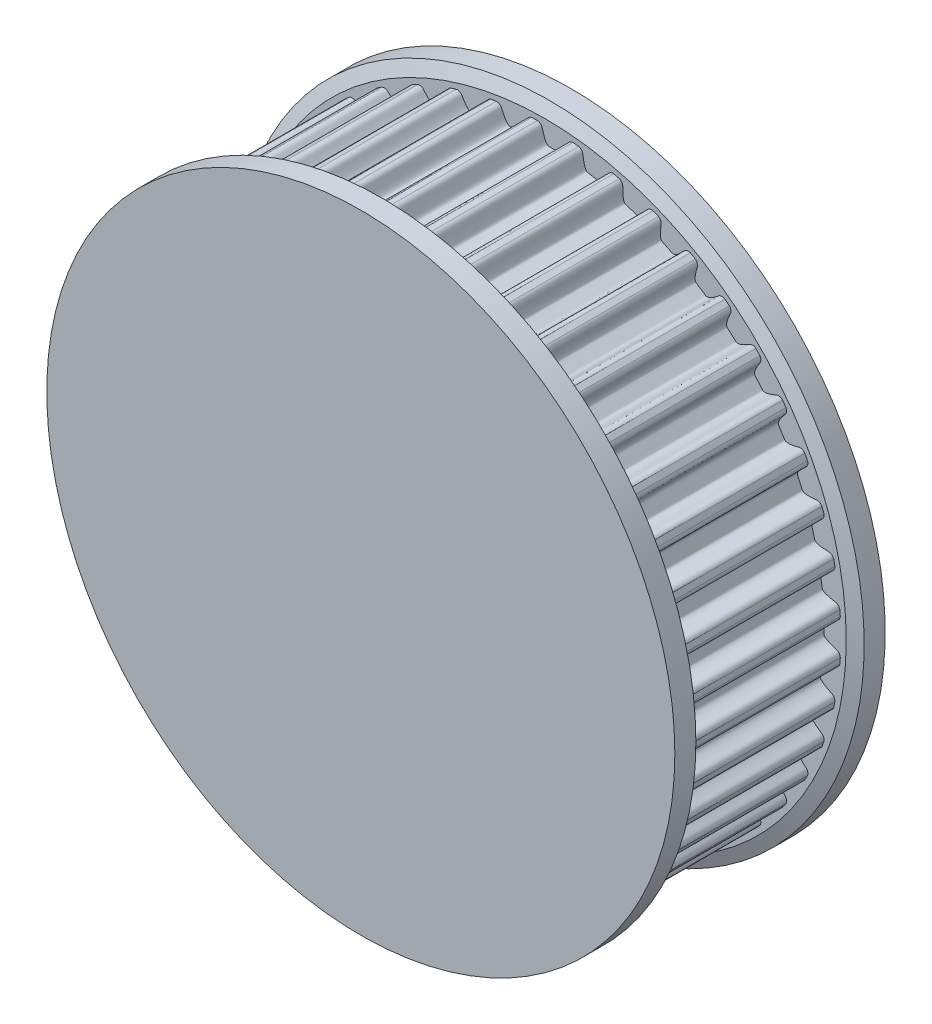
SolidWorks part; units mm, degrees
ref_plane "Front Plane" through (0, 0, 0) normal (0, 0, 1) x (1, 0, 0)
ref_plane "Top Plane" through (0, 0, 0) normal (0, 1, 0) x (1, 0, 0)
ref_plane "Right Plane" through (0, 0, 0) normal (1, 0, 0) x (0, 0, -1)
ref_axis "Axis1" through (0, 0, 55) along (0, 0, -1)
sketch "SketchRevolveGearBelt01" plane through (0, 0, 0) normal (1, 0, 0) x (0, 0, -1)
  line L0 (0, 0) -> (1, 0) construction
  line L1 (5.274, 0) -> (5.274, 12.8239)
  line L2 (5.274, 12.8239) -> (4.512, 12.8239)
  line L3 (4.512, 12.8239) -> (4.512, 14.1724)
  line L4 (4.512, 14.1724) -> (4.7696, 14.7943)
  line L5 (4.7696, 14.7943) -> (4.0656, 15.0859)
  line L6 (4.0656, 15.0859) -> (3.75, 14.3239)
  line L7 (3.75, 14.3239) -> (3.75, 14.0678)
  line L8 (3.75, 14.0678) -> (-3.75, 14.0678)
  line L9 (-3.75, 14.0678) -> (-3.75, 14.3239)
  line L10 (-3.75, 14.3239) -> (-4.0656, 15.0859)
  line L11 (-4.0656, 15.0859) -> (-4.7696, 14.7943)
  line L12 (-4.7696, 14.7943) -> (-4.512, 14.1724)
  line L13 (-4.512, 14.1724) -> (-4.512, 12.8239)
  line L14 (-4.512, 12.8239) -> (-5.274, 12.8239)
  line L15 (-5.274, 12.8239) -> (-5.274, 0)
  line L16 (-5.274, 0) -> (5.274, 0)
  dimension "GearBeltSide1" = 5.274
  dimension "GearBeltFlange1OutsideWidth" = 4.512
  dimension "GearBeltFlange1OutsideLength" = 1.3484
  dimension "GearBeltFlange1X" = 0.2576
  dimension "GearBeltFlange1Y" = 0.622
  dimension "GearBeltFlangeThickness" = 0.762
  dimension "GearBeltToothWidth1" = 3.75
  dimension "GearBeltFlangeInside" = 0.2561
  dimension "GearBeltOutsideDiameter" = 14.0678
  dimension "GearBeltToothWidth2" = 3.75
  dimension "GearBeltFlange2X" = 0.2576
  dimension "GearBeltFlange2OutsideWidth" = 4.512
revolve "GearBelt01" add sketch "SketchRevolveGearBelt01" angle 360 about L0
sketch "SketchToothGearBelt01" plane through (0, 0, 0) normal (0, 0, 1) x (1, 0, 0)
  arc A0 (14.0431, 0.8614) -> (14.0431, -0.8614) centre (0, 0) cw
  spline S0 degree 3 poles (14.0431, -0.8614) (14.0431, -0.8441) (14.0405, -0.8182) (14.0321, -0.7847) (14.0235, -0.7603) (14.0125, -0.7368) (13.9993, -0.7146) (13.9839, -0.6937) (13.9667, -0.6743) (13.9476, -0.6568) (13.9269, -0.6412) (13.9048, -0.6276) (13.8816, -0.6162) (13.8415, -0.602) (13.7904, -0.5865) (13.7301, -0.5675) (13.6777, -0.5498) (13.6284, -0.5322) (13.5823, -0.5145) (13.5394, -0.4969) (13.4996, -0.4793) (13.463, -0.4616) (13.4296, -0.444) (13.3993, -0.4264) (13.3722, -0.4087) (13.3483, -0.3911) (13.3275, -0.3735) (13.3099, -0.3558) (13.2955, -0.3381) (13.2841, -0.3203) (13.276, -0.3025) (13.271, -0.2846) (13.2688, -0.2503) (13.272, -0.2) (13.2721, -0.1333) (13.2729, -0.0667) (13.273, 0) (13.2729, 0.0667) (13.2721, 0.1333) (13.272, 0.2) (13.2688, 0.2503) (13.271, 0.2846) (13.276, 0.3025) (13.2841, 0.3203) (13.2955, 0.3381) (13.3099, 0.3558) (13.3275, 0.3735) (13.3483, 0.3911) (13.3722, 0.4087) (13.3993, 0.4264) (13.4296, 0.444) (13.463, 0.4616) (13.4996, 0.4793) (13.5394, 0.4969) (13.5823, 0.5145) (13.6284, 0.5322) (13.6777, 0.5498) (13.7301, 0.5675) (13.7904, 0.5865) (13.8415, 0.602) (13.8816, 0.6162) (13.9048, 0.6276) (13.9269, 0.6412) (13.9476, 0.6568) (13.9667, 0.6743) (13.9839, 0.6937) (13.9993, 0.7146) (14.0125, 0.7368) (14.0235, 0.7603) (14.0321, 0.7847) (14.0405, 0.8182) (14.0431, 0.8441) (14.0431, 0.8614) knots 0 0 0 0 0.01974 0.029611 0.039481 0.049351 0.059221 0.069092 0.078962 0.088832 0.098702 0.108572 0.118443 0.128313 0.157265 0.17953 0.200642 0.220609 0.23944 0.257143 0.273731 0.28922 0.303626 0.316973 0.329289 0.340609 0.35098 0.360462 0.369135 0.377101 0.384492 0.391474 0.398242 0.4237 0.449134 0.474567 0.5 0.525433 0.550866 0.5763 0.601758 0.608526 0.615508 0.622899 0.630865 0.639538 0.64902 0.659391 0.670711 0.683027 0.696374 0.71078 0.726269 0.742857 0.76056 0.779391 0.799358 0.82047 0.842735 0.871687 0.881557 0.891428 0.901298 0.911168 0.921038 0.930908 0.940779 0.950649 0.960519 0.970389 0.98026 1 1 1 1
extrude "ToothExtrudeCutGearBelt01" cut sketch "SketchToothGearBelt01" against normal blind 3.75 and the other way blind 3.75
pattern_circular "PatternGearBelt01" count 45 every 8 about axis through (0, 0, 55) along (0, 0, -1) of "ToothExtrudeCutGearBelt01"
sketch "BoreRevolveSketch" plane through (0, 0, 0) normal (1, 0, 0) x (0, 0, -1)
  line L0 (0, 0) -> (1, 0) construction
  line L1 (-5.274, 0) -> (5.274, 0)
  line L2 (5.274, 0) -> (5.274, 5)
  line L3 (5.274, 5) -> (-5.274, 5)
  line L4 (-5.274, 5) -> (-5.274, 0)
  dimension "BoreSide1" = 5.274
  dimension "TaperSide1" = 5
  dimension "BoreSide2" = 5.274
  dimension "TaperSide2" = 5
revolve "BoreRevolveCut" cut sketch "BoreRevolveSketch" angle 360 about L0
sketch "AuxiliarySketchGearBelt01" plane through (0, 0, 0) normal (0, 0, 1) x (1, 0, 0)
  circle A0 centre (0, 0) radius 14.3239 construction
  dimension "PitchDiameter" = 28.6479
sketch "Sketch1" plane through (0, 0, 0) normal (0, 1, 0) x (1, 0, 0)
  line L0 (0, 0) -> (22.5246, 0) construction
  line L1 (38.9449, 21.6156) -> (-58.827, 21.6156)
  line L2 (38.9449, 21.6156) -> (38.9449, 4)
  line L3 (38.9449, 4) -> (-58.827, 4)
  line L4 (-58.827, 21.6156) -> (-58.827, 4)
  line L5 (38.9449, 21.6156) -> (-58.827, 4) construction
  line L6 (38.9449, 4) -> (-58.827, 21.6156) construction
  line L7 (-14.3239, 0) -> (14.3239, 0) construction
  line L8 (38.9449, -21.6156) -> (38.9449, -4)
  line L9 (38.9449, -21.6156) -> (-58.827, -21.6156)
  line L10 (-58.827, -21.6156) -> (-58.827, -4)
  line L11 (38.9449, -4) -> (-58.827, -4)
  point P4 (-9.9411, 12.8078)
  dimension "D1" = 4
extrude "Cut-Extrude1" cut sketch "Sketch1" against normal through all both and the other way through all
sketch "Sketch2" plane through (0, 0, 4) normal (0, 0, 1) x (1, 0, 0)
  circle A1 centre (0, 0) radius 14.9275
  circle A2 centre (0, 0) radius 14.9275
  dimension "D1" = 0
extrude "Boss-Extrude1" add sketch "Sketch2" along normal blind 1
sketch "Sketch3" plane through (0, 0, -4) normal (0, 0, -1) x (-1, 0, 0)
  circle A0 centre (0, 0) radius 7.1791
extrude "Boss-Extrude2" add sketch "Sketch3" against normal up to surface (8 mm away) up to face at (-5, 0, 4)
sketch "Sketch4" plane through (0, 0, -4) normal (0, 0, -1) x (-1, 0, 0)
  circle A1 centre (0, 0) radius 14.9275
  circle A2 centre (0, 0) radius 14.9275
  dimension "D1" = 0
extrude "Boss-Extrude3" add sketch "Sketch4" along normal blind 1
